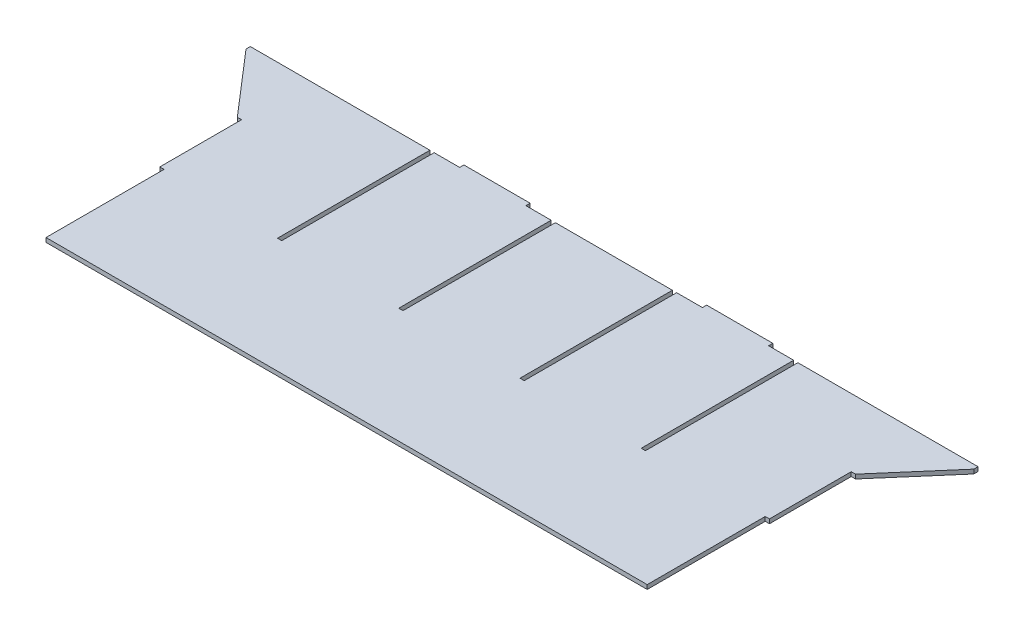
SolidWorks part; units mm, degrees
material "6061-T6 (SS)"
ref_plane "X-Y Datum" through (0, 0, 0) normal (0, 0, 1) x (1, 0, 0)
ref_plane "X-Z Datum" through (0, 0, 0) normal (0, 1, 0) x (1, 0, 0)
ref_plane "Y-Z Datum" through (0, 0, 0) normal (1, 0, 0) x (0, 0, -1)
sketch "Sketch1" plane through (0, 0, 0) normal (0, 0, 1) x (1, 0, 0)
  line L1 (-228.6115, -1.5875) -> (228.6115, -1.5875)
  line L2 (-228.6115, -1.5875) -> (-228.6115, 1.5875)
  line L3 (-228.6115, 1.5875) -> (228.6115, 1.5875)
  line L4 (228.6115, -1.5875) -> (228.6115, 1.5875)
  line L5 (-228.6115, -1.5875) -> (228.6115, 1.5875) construction
  line L6 (-228.6115, 1.5875) -> (228.6115, -1.5875) construction
  point P0 (0, 0)
  dimension "D1" = 3.175
  dimension "D2" = 457.223
extrude "Boss-Extrude1" add sketch "Sketch1" along normal blind 200.642
sketch "Sketch2" plane through (0, 1.5875, 0) normal (0, 1, 0) x (1, 0, 0)
  line L0 (228.6115, 0) -> (225.4365, 0)
  line L1 (228.6115, 0) -> (-228.6115, 0) construction
  line L2 (225.4365, 0) -> (137.8065, 0)
  line L3 (137.8065, 0) -> (134.6315, 0)
  line L10 (134.6315, 0) -> (137.8065, 0)
  line L11 (134.6315, 0) -> (134.6315, -114.3)
  line L12 (134.6315, -114.3) -> (137.8065, -114.3)
  line L13 (137.8065, 0) -> (137.8065, -114.3)
  line M2 (228.6115, 0) -> (-228.6115, 0)
  dimension "D1" = 87.63
  dimension "D2" = 3.175
  dimension "D3" = 114.3
  dimension "D4" = 3.175
extrude "Cut-Extrude1" cut sketch "Sketch2" against normal through all contours L13 L11 L12 M2 region at (136.219, 1.5875, 57.15)
pattern_linear "LPattern1" count 4 spacing 90.932 along (-1, 0, 0) of "Cut-Extrude1"
sketch "Sketch3" plane through (0, 0, 0) normal (0, 0, -1) x (-1, 0, 0)
  line L0 (-66.1907, -1.5583) -> (-66.1907, -1.5875)
  line L9 (-46.8745, -1.5875) -> (-134.6315, -1.5875) construction
  line L11 (-134.6315, 1.5875) -> (-46.8745, 1.5875) construction
  line L12 (47.2325, 1.5875) -> (134.9895, 1.5875) construction
  line L13 (-66.1907, -1.5875) -> (-115.8495, -1.5875)
  line L14 (-66.1907, -1.5875) -> (-66.1907, 1.5875)
  line L15 (-66.1907, 1.5875) -> (-115.8495, 1.5875)
  line L16 (-115.8495, -1.5875) -> (-115.8495, 1.5875)
  line L17 (66.1907, -1.5875) -> (115.8495, -1.5875)
  line L18 (66.1907, -1.5875) -> (66.1907, 1.5875)
  line L19 (66.1907, 1.5875) -> (115.8495, 1.5875)
  line L20 (115.8495, -1.5875) -> (115.8495, 1.5875)
  line M4 (-46.8745, 1.5875) -> (-134.6315, 1.5875)
  dimension "D2" = 49.6588
sketch "Sketch4" plane through (0, -1.5875, 0) normal (0, -1, 0) x (1, 0, 0)
  line L0 (-228.6115, 0) -> (-272.8865, 0)
  line L2 (-228.6115, 200.642) -> (-228.6115, 0) construction
  line L3 (-228.6115, 50.8) -> (-228.6115, 0)
  line L4 (-272.8865, 0) -> (-272.8865, 3.175)
  line L6 (-228.6115, 50.8) -> (-231.7865, 50.8)
  line L7 (-272.8865, 3.175) -> (-231.7865, 50.8)
  dimension "D1" = 44.275
  dimension "D2" = 50.8
  dimension "D3" = 3.175
extrude "Boss-Extrude3" add sketch "Sketch4" against normal blind 3.175
mirror "Mirror1" about plane through (0, 0, 0) normal (1, 0, 0) of "Boss-Extrude3"
sketch "Sketch5" plane through (0, -1.5875, 0) normal (0, -1, 0) x (1, 0, 0)
  line L1 (-228.6115, 200.642) -> (-225.4365, 200.642)
  line L2 (-228.6115, 200.642) -> (-228.6115, 112.128)
  line L3 (-228.6115, 112.128) -> (-225.4365, 112.128)
  line L4 (-225.4365, 200.642) -> (-225.4365, 112.128)
  dimension "D1" = 3.175
  dimension "D2" = 88.514
extrude "Cut-Extrude2" cut sketch "Sketch5" against normal blind 3.175
mirror "Mirror2" about plane through (0, 0, 0) normal (1, 0, 0) of "Cut-Extrude2"
extrude "Boss-Extrude4" add sketch "Sketch3" along normal blind 3.18 contours M4 | L17 region at (91.0201, 0, 0) region at (-91.0201, 0, 0)
